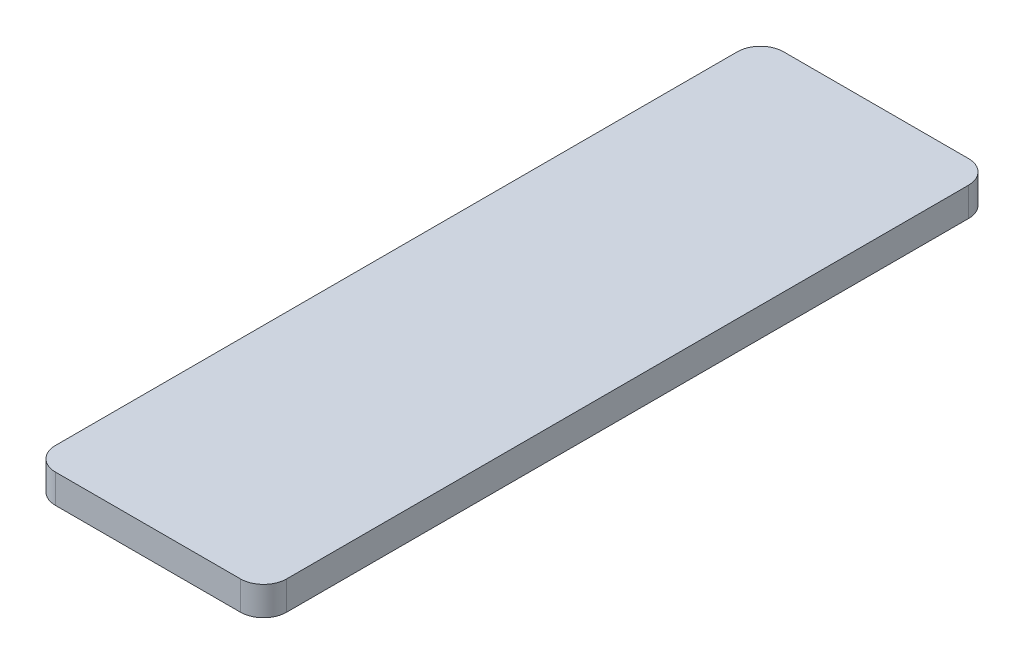
SolidWorks part; units mm, degrees
material "Acrylic (Medium-high impact)"
ref_plane "Front Plane" through (0, 0, 0) normal (0, 0, 1) x (1, 0, 0)
ref_plane "Top Plane" through (0, 0, 0) normal (0, 1, 0) x (1, 0, 0)
ref_plane "Right Plane" through (0, 0, 0) normal (1, 0, 0) x (0, 0, -1)
ref_plane "Plane1" through (0, 0, 0) normal (0, 1, 0) x (1, 0, 0)
sketch "Sketch1" plane through (0, 0, 0) normal (0, 1, 0) x (1, 0, 0)
  line L1 (-26.2811, -23.7838) -> (-0.8811, -23.7838)
  line L2 (-26.2811, -23.7838) -> (-26.2811, 56.2162)
  line L3 (-26.2811, 56.2162) -> (-0.8811, 56.2162)
  line L4 (-0.8811, -23.7838) -> (-0.8811, 56.2162)
  dimension "D1" = 80
  dimension "D2" = 25.4
extrude "Boss-Extrude1" add sketch "Sketch1" along normal blind 3.175
fillet "Fillet1" radius 2.54 4 edges at (-26.2811, 1.5875, -56.2162) (-0.8811, 1.5875, -56.2162) (-0.8811, 1.5875, 23.7838) (-26.2811, 1.5875, 23.7838)
